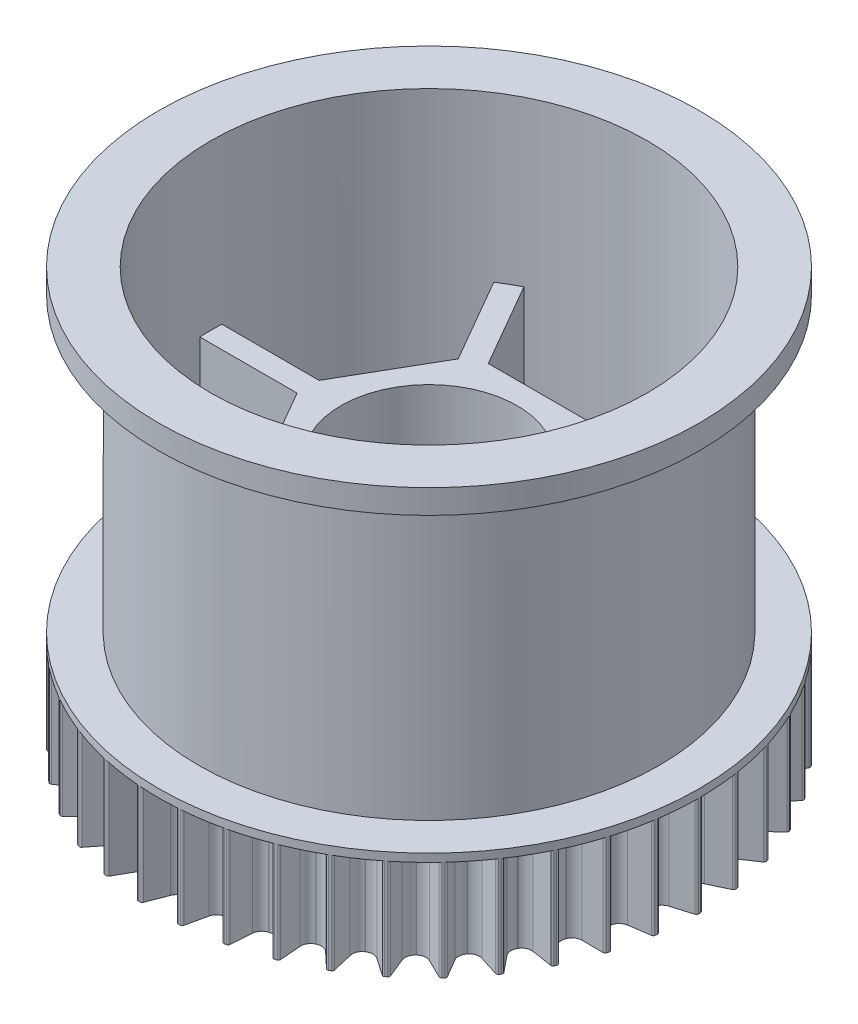
SolidWorks part; units mm, degrees
ref_plane "前视基准面" through (0, 0, 0) normal (0, 0, 1) x (1, 0, 0)
ref_plane "上视基准面" through (0, 0, 0) normal (0, 1, 0) x (1, 0, 0)
ref_plane "右视基准面" through (0, 0, 0) normal (1, 0, 0) x (0, 0, -1)
other "Configuration Table"
sketch "草图1" plane through (0, 0, 0) normal (0, 1, 0) x (1, 0, 0)
  line L0 (0, 0) -> (7.9279, 0) construction
  line L1 (0, 0) -> (0, 4.4256) construction
  line L2 (12.4216, 0.4494) -> (13.4287, 0.1463)
  line L3 (12.4216, -0.4494) -> (13.4287, -0.1463)
  line L4 (12.2159, -2.2957) -> (13.2569, -2.1461)
  line L5 (12.3499, -1.407) -> (13.3005, -1.8568)
  line L6 (11.7373, -4.0908) -> (12.789, -4.098)
  line L7 (12.0023, -3.2319) -> (12.8752, -3.8184)
  line L8 (10.9965, -5.7945) -> (12.0354, -5.9583)
  line L9 (11.3865, -4.9846) -> (12.1623, -5.6947)
  line L10 (10.0101, -7.3687) -> (11.0129, -7.6855)
  line L11 (10.5164, -6.626) -> (11.1777, -7.4438)
  line L12 (8.8, -8.7783) -> (9.7445, -9.2411)
  line L13 (9.4114, -8.1194) -> (9.9434, -9.0266)
  line L14 (7.3934, -9.9918) -> (8.2583, -10.5902)
  line L15 (8.0961, -9.4314) -> (8.487, -10.4078)
  line L16 (5.8216, -10.9822) -> (6.5877, -11.7028)
  line L17 (6.6, -10.5328) -> (6.841, -11.5565)
  line L18 (4.1198, -11.7272) -> (4.7699, -12.5539)
  line L19 (4.9565, -11.3988) -> (5.0422, -12.447)
  line L20 (2.3259, -12.2102) -> (2.8456, -13.1246)
  line L21 (3.2022, -12.0102) -> (3.1308, -13.0595)
  line L22 (0.4801, -12.4205) -> (0.8577, -13.4021)
  line L23 (1.3764, -12.3533) -> (1.1494, -13.3802)
  line L24 (-1.3764, -12.3533) -> (-1.1494, -13.3802)
  line L25 (-0.4801, -12.4205) -> (-0.8577, -13.4021)
  line L26 (-3.2022, -12.0102) -> (-3.1308, -13.0595)
  line L27 (-2.3259, -12.2102) -> (-2.8456, -13.1246)
  line L28 (-4.9565, -11.3988) -> (-5.0422, -12.447)
  line L29 (-4.1198, -11.7272) -> (-4.7699, -12.5539)
  line L30 (-6.6, -10.5328) -> (-6.841, -11.5565)
  line L31 (-5.8216, -10.9822) -> (-6.5877, -11.7028)
  line L32 (-8.0961, -9.4314) -> (-8.487, -10.4078)
  line L33 (-7.3934, -9.9918) -> (-8.2583, -10.5902)
  line L34 (-9.4114, -8.1194) -> (-9.9434, -9.0266)
  line L35 (-8.8, -8.7783) -> (-9.7445, -9.2411)
  line L36 (-10.5164, -6.626) -> (-11.1777, -7.4438)
  line L37 (-10.0101, -7.3687) -> (-11.0129, -7.6855)
  line L38 (-11.3865, -4.9846) -> (-12.1623, -5.6947)
  line L39 (-10.9965, -5.7945) -> (-12.0354, -5.9583)
  line L40 (-12.0023, -3.2319) -> (-12.8752, -3.8184)
  line L41 (-11.7373, -4.0908) -> (-12.789, -4.098)
  line L42 (-12.3499, -1.407) -> (-13.3005, -1.8568)
  line L43 (-12.2159, -2.2957) -> (-13.2569, -2.1461)
  line L44 (-12.4216, 0.4494) -> (-13.4287, 0.1463)
  line L45 (-12.4216, -0.4494) -> (-13.4287, -0.1463)
  line L46 (-12.2159, 2.2957) -> (-13.2569, 2.1461)
  line L47 (-12.3499, 1.407) -> (-13.3005, 1.8568)
  line L48 (-11.7373, 4.0908) -> (-12.789, 4.098)
  line L49 (-12.0023, 3.2319) -> (-12.8752, 3.8184)
  line L50 (-10.9965, 5.7945) -> (-12.0354, 5.9583)
  line L51 (-11.3865, 4.9846) -> (-12.1623, 5.6947)
  line L52 (-10.0101, 7.3687) -> (-11.0129, 7.6855)
  line L53 (-10.5164, 6.626) -> (-11.1777, 7.4438)
  line L54 (-8.8, 8.7783) -> (-9.7445, 9.2411)
  line L55 (-9.4114, 8.1194) -> (-9.9434, 9.0266)
  line L56 (-7.3934, 9.9918) -> (-8.2583, 10.5902)
  line L57 (-8.0961, 9.4314) -> (-8.487, 10.4078)
  line L58 (-5.8216, 10.9822) -> (-6.5877, 11.7028)
  line L59 (-6.6, 10.5328) -> (-6.841, 11.5565)
  line L60 (-4.1198, 11.7272) -> (-4.7699, 12.5539)
  line L61 (-4.9565, 11.3988) -> (-5.0422, 12.447)
  line L62 (-2.3259, 12.2102) -> (-2.8456, 13.1246)
  line L63 (-3.2022, 12.0102) -> (-3.1308, 13.0595)
  line L64 (-0.4801, 12.4205) -> (-0.8577, 13.4021)
  line L65 (-1.3764, 12.3533) -> (-1.1494, 13.3802)
  line L66 (1.3764, 12.3533) -> (1.1494, 13.3802)
  line L67 (0.4801, 12.4205) -> (0.8577, 13.4021)
  line L68 (3.2022, 12.0102) -> (3.1308, 13.0595)
  line L69 (2.3259, 12.2102) -> (2.8456, 13.1246)
  line L70 (4.9565, 11.3988) -> (5.0422, 12.447)
  line L71 (4.1198, 11.7272) -> (4.7699, 12.5539)
  line L72 (6.6, 10.5328) -> (6.841, 11.5565)
  line L73 (5.8216, 10.9822) -> (6.5877, 11.7028)
  line L74 (8.0961, 9.4314) -> (8.487, 10.4078)
  line L75 (7.3934, 9.9918) -> (8.2583, 10.5902)
  line L76 (9.4114, 8.1194) -> (9.9434, 9.0266)
  line L77 (8.8, 8.7783) -> (9.7445, 9.2411)
  line L78 (10.5164, 6.626) -> (11.1777, 7.4438)
  line L79 (10.0101, 7.3687) -> (11.0129, 7.6855)
  line L80 (11.3865, 4.9846) -> (12.1623, 5.6947)
  line L81 (10.9965, 5.7945) -> (12.0354, 5.9583)
  line L82 (12.0023, 3.2319) -> (12.8752, 3.8184)
  line L83 (11.7373, 4.0908) -> (12.789, 4.098)
  line L84 (12.3499, 1.407) -> (13.3005, 1.8568)
  line L85 (12.2159, 2.2957) -> (13.2569, 2.1461)
  line L95 (3.1754, 5.5) -> (-3.1754, 5.5) construction
  line L96 (3.1754, 5.5) -> (6.0333, 0.55) construction
  line L97 (0, 0) -> (3.1754, 5.5) construction
  line L98 (-3.1754, 5.5) -> (-6.0333, 0.55) construction
  line L99 (3.493, -4.95) -> (6.0333, -0.55)
  line L100 (2.5403, -5.5) -> (-2.5403, -5.5)
  line L101 (-3.493, -4.95) -> (-6.0333, -0.55)
  line L102 (8.1752, 0) -> (11.2, 0) construction
  line L103 (6.0333, 0.55) -> (11.1865, 0.55)
  line L104 (6.0333, -0.55) -> (11.1865, -0.55)
  line L105 (3.493, -4.95) -> (6.0696, -9.4128)
  line L106 (2.5403, -5.5) -> (5.1169, -9.9628)
  line L107 (-2.5403, -5.5) -> (-5.1169, -9.9628)
  line L108 (-3.493, -4.95) -> (-6.0696, -9.4128)
  line L109 (-6.0333, -0.55) -> (-11.1865, -0.55)
  line L110 (-6.0333, 0.55) -> (-11.1865, 0.55)
  line L111 (-3.493, 4.95) -> (-6.0696, 9.4128)
  line L112 (-2.5403, 5.5) -> (-5.1169, 9.9628)
  line L113 (2.5403, 5.5) -> (5.1169, 9.9628)
  line L114 (3.493, 4.95) -> (6.0696, 9.4128)
  line L115 (0, 0) -> (12.0337, 1.2648) construction
  line L116 (12.0337, -1.2648) -> (0, 0) construction
  line L117 (-6.0333, 0.55) -> (-3.493, 4.95)
  line L118 (-2.5403, 5.5) -> (2.5403, 5.5)
  line L119 (3.493, 4.95) -> (6.0333, 0.55)
  circle A0 centre (0, 0) radius 11.2 construction
  circle A1 centre (0, 0) radius 12.1 construction
  circle A2 centre (0, 0) radius 13.5 construction
  arc A3 (13.4999, 0.0509) -> (13.4999, -0.0509) centre (0, 0) cw
  arc A4 (12.0671, 0.8914) -> (12.0337, 1.2648) centre (0, 0) ccw construction
  arc A5 (13.4287, -0.1463) -> (13.4999, -0.0509) centre (13.3999, -0.0505) ccw
  arc A6 (13.4287, 0.1463) -> (13.4999, 0.0509) centre (13.3999, 0.0505) cw
  arc A7 (12.0671, -0.8914) -> (12.0337, -1.2648) centre (0, 0) cw construction
  arc A8 (12.4216, -0.4494) -> (12.0671, -0.8914) centre (12.5658, -0.9282) ccw
  arc A9 (12.4216, 0.4494) -> (12.0671, 0.8914) centre (12.5658, 0.9282) cw
  arc A10 (12.2159, -2.2957) -> (11.7995, -2.6799) centre (12.2871, -2.7907) ccw
  arc A11 (12.3499, -1.407) -> (12.0652, -0.9171) centre (12.5638, -0.955) cw
  arc A12 (13.3005, -1.8568) -> (13.3567, -1.9617) centre (13.2578, -1.9472) cw
  arc A13 (13.3567, -1.9617) -> (13.3415, -2.0624) centre (0, 0) cw
  arc A14 (13.2569, -2.1461) -> (13.3415, -2.0624) centre (13.2427, -2.0471) ccw
  arc A15 (11.7373, -4.0908) -> (11.2683, -4.4086) centre (11.7339, -4.5908) ccw
  arc A16 (12.0023, -3.2319) -> (11.7937, -2.7051) centre (12.2811, -2.8169) cw
  arc A17 (12.8752, -3.8184) -> (12.9151, -3.9305) centre (12.8195, -3.9014) cw
  arc A18 (12.9151, -3.9305) -> (12.8851, -4.0278) centre (0, 0) cw
  arc A19 (12.789, -4.098) -> (12.8851, -4.0278) centre (12.7897, -3.998) ccw
  arc A20 (10.9965, -5.7945) -> (10.4854, -6.0388) centre (10.9186, -6.2884) ccw
  arc A21 (11.3865, -4.9846) -> (11.2589, -4.4326) centre (11.7241, -4.6158) cw
  arc A22 (12.1623, -5.6947) -> (12.1851, -5.8115) centre (12.0948, -5.7685) cw
  arc A23 (12.1851, -5.8115) -> (12.1409, -5.9032) centre (0, 0) cw
  arc A24 (12.0354, -5.9583) -> (12.1409, -5.9032) centre (12.051, -5.8595) ccw
  arc A25 (10.0101, -7.3687) -> (9.4682, -7.5341) centre (9.8595, -7.8455) ccw
  arc A26 (10.5164, -6.626) -> (10.4724, -6.0612) centre (10.9052, -6.3116) cw
  arc A27 (11.1777, -7.4438) -> (11.1828, -7.5627) centre (11.1, -7.5067) cw
  arc A28 (11.1828, -7.5627) -> (11.1255, -7.6468) centre (0, 0) cw
  arc A29 (11.0129, -7.6855) -> (11.1255, -7.6468) centre (11.0431, -7.5902) ccw
  arc A30 (8.8, -8.7783) -> (8.2395, -8.8611) centre (8.58, -9.2273) ccw
  arc A31 (9.4114, -8.1194) -> (9.4521, -7.5543) centre (9.8427, -7.8665) cw
  arc A32 (9.9434, -9.0266) -> (9.9308, -9.145) centre (9.8572, -9.0772) cw
  arc A33 (9.9308, -9.145) -> (9.8615, -9.2196) centre (0, 0) cw
  arc A34 (9.7445, -9.2411) -> (9.8615, -9.2196) centre (9.7885, -9.1513) ccw
  arc A35 (7.3934, -9.9918) -> (6.8268, -9.9902) centre (7.1089, -10.403) ccw
  arc A36 (8.0961, -9.4314) -> (8.2206, -8.8787) centre (8.5603, -9.2456) cw
  arc A37 (8.487, -10.4078) -> (8.4568, -10.5229) centre (8.3942, -10.445) cw
  arc A38 (8.4568, -10.5229) -> (8.3773, -10.5864) centre (0, 0) cw
  arc A39 (8.2583, -10.5902) -> (8.3773, -10.5864) centre (8.3152, -10.508) ccw
  arc A40 (5.8216, -10.9822) -> (5.2616, -10.8961) centre (5.479, -11.3464) ccw
  arc A41 (6.6, -10.5328) -> (6.8055, -10.0048) centre (7.0867, -10.4182) cw
  arc A42 (6.841, -11.5565) -> (6.794, -11.6658) centre (6.7437, -11.5794) cw
  arc A43 (6.794, -11.6658) -> (6.7059, -11.7167) centre (0, 0) cw
  arc A44 (6.5877, -11.7028) -> (6.7059, -11.7167) centre (6.6562, -11.6299) ccw
  arc A45 (4.1198, -11.7272) -> (3.5789, -11.5586) centre (3.7268, -12.0362) ccw
  arc A46 (4.9565, -11.3988) -> (5.2384, -10.9073) centre (5.4548, -11.358) cw
  arc A47 (5.0422, -12.447) -> (4.9795, -12.5481) centre (4.9426, -12.4552) cw
  arc A48 (4.9795, -12.5481) -> (4.8847, -12.5853) centre (0, 0) cw
  arc A49 (4.7699, -12.5539) -> (4.8847, -12.5853) centre (4.8485, -12.4921) ccw
  arc A50 (2.3259, -12.2102) -> (1.8162, -11.9629) centre (1.8912, -12.4573) ccw
  arc A51 (3.2022, -12.0102) -> (3.5542, -11.5662) centre (3.7011, -12.0442) cw
  arc A52 (3.1308, -13.0595) -> (3.0536, -13.1501) centre (3.031, -13.0527) cw
  arc A53 (3.0536, -13.1501) -> (2.9544, -13.1728) centre (0, 0) cw
  arc A54 (2.8456, -13.1246) -> (2.9544, -13.1728) centre (2.9325, -13.0752) ccw
  arc A55 (0.4801, -12.4205) -> (0.0129, -12.1) centre (0.0134, -12.6) ccw
  arc A56 (1.3764, -12.3533) -> (1.7906, -11.9668) centre (1.8646, -12.4613) cw
  arc A57 (1.1494, -13.3802) -> (1.0596, -13.4584) centre (1.0518, -13.3587) cw
  arc A58 (1.0596, -13.4584) -> (0.9581, -13.466) centre (0, 0) cw
  arc A59 (0.8577, -13.4021) -> (0.9581, -13.466) centre (0.951, -13.3662) ccw
  arc A60 (-1.3764, -12.3533) -> (-1.7906, -11.9668) centre (-1.8646, -12.4613) ccw
  arc A61 (-0.4801, -12.4205) -> (-0.0129, -12.1) centre (-0.0134, -12.6) cw
  arc A62 (-0.8577, -13.4021) -> (-0.9581, -13.466) centre (-0.951, -13.3662) cw
  arc A63 (-0.9581, -13.466) -> (-1.0596, -13.4584) centre (0, 0) cw
  arc A64 (-1.1494, -13.3802) -> (-1.0596, -13.4584) centre (-1.0518, -13.3587) ccw
  arc A65 (-3.2022, -12.0102) -> (-3.5542, -11.5662) centre (-3.7011, -12.0442) ccw
  arc A66 (-2.3259, -12.2102) -> (-1.8162, -11.9629) centre (-1.8912, -12.4573) cw
  arc A67 (-2.8456, -13.1246) -> (-2.9544, -13.1728) centre (-2.9325, -13.0752) cw
  arc A68 (-2.9544, -13.1728) -> (-3.0536, -13.1501) centre (0, 0) cw
  arc A69 (-3.1308, -13.0595) -> (-3.0536, -13.1501) centre (-3.031, -13.0527) ccw
  arc A70 (-4.9565, -11.3988) -> (-5.2384, -10.9073) centre (-5.4548, -11.358) ccw
  arc A71 (-4.1198, -11.7272) -> (-3.5789, -11.5586) centre (-3.7268, -12.0362) cw
  arc A72 (-4.7699, -12.5539) -> (-4.8847, -12.5853) centre (-4.8485, -12.4921) cw
  arc A73 (-4.8847, -12.5853) -> (-4.9795, -12.5481) centre (0, 0) cw
  arc A74 (-5.0422, -12.447) -> (-4.9795, -12.5481) centre (-4.9426, -12.4552) ccw
  arc A75 (-6.6, -10.5328) -> (-6.8055, -10.0048) centre (-7.0867, -10.4182) ccw
  arc A76 (-5.8216, -10.9822) -> (-5.2616, -10.8961) centre (-5.479, -11.3464) cw
  arc A77 (-6.5877, -11.7028) -> (-6.7059, -11.7167) centre (-6.6562, -11.6299) cw
  arc A78 (-6.7059, -11.7167) -> (-6.794, -11.6658) centre (0, 0) cw
  arc A79 (-6.841, -11.5565) -> (-6.794, -11.6658) centre (-6.7437, -11.5794) ccw
  arc A80 (-8.0961, -9.4314) -> (-8.2206, -8.8787) centre (-8.5603, -9.2456) ccw
  arc A81 (-7.3934, -9.9918) -> (-6.8268, -9.9902) centre (-7.1089, -10.403) cw
  arc A82 (-8.2583, -10.5902) -> (-8.3773, -10.5864) centre (-8.3152, -10.508) cw
  arc A83 (-8.3773, -10.5864) -> (-8.4568, -10.5229) centre (0, 0) cw
  arc A84 (-8.487, -10.4078) -> (-8.4568, -10.5229) centre (-8.3942, -10.445) ccw
  arc A85 (-9.4114, -8.1194) -> (-9.4521, -7.5543) centre (-9.8427, -7.8665) ccw
  arc A86 (-8.8, -8.7783) -> (-8.2395, -8.8611) centre (-8.58, -9.2273) cw
  arc A87 (-9.7445, -9.2411) -> (-9.8615, -9.2196) centre (-9.7885, -9.1513) cw
  arc A88 (-9.8615, -9.2196) -> (-9.9308, -9.145) centre (0, 0) cw
  arc A89 (-9.9434, -9.0266) -> (-9.9308, -9.145) centre (-9.8572, -9.0772) ccw
  arc A90 (-10.5164, -6.626) -> (-10.4724, -6.0612) centre (-10.9052, -6.3116) ccw
  arc A91 (-10.0101, -7.3687) -> (-9.4682, -7.5341) centre (-9.8595, -7.8455) cw
  arc A92 (-11.0129, -7.6855) -> (-11.1255, -7.6468) centre (-11.0431, -7.5902) cw
  arc A93 (-11.1255, -7.6468) -> (-11.1828, -7.5627) centre (0, 0) cw
  arc A94 (-11.1777, -7.4438) -> (-11.1828, -7.5627) centre (-11.1, -7.5067) ccw
  arc A95 (-11.3865, -4.9846) -> (-11.2589, -4.4326) centre (-11.7241, -4.6158) ccw
  arc A96 (-10.9965, -5.7945) -> (-10.4854, -6.0388) centre (-10.9186, -6.2884) cw
  arc A97 (-12.0354, -5.9583) -> (-12.1409, -5.9032) centre (-12.051, -5.8595) cw
  arc A98 (-12.1409, -5.9032) -> (-12.1851, -5.8115) centre (0, 0) cw
  arc A99 (-12.1623, -5.6947) -> (-12.1851, -5.8115) centre (-12.0948, -5.7685) ccw
  arc A100 (-12.0023, -3.2319) -> (-11.7937, -2.7051) centre (-12.2811, -2.8169) ccw
  arc A101 (-11.7373, -4.0908) -> (-11.2683, -4.4086) centre (-11.7339, -4.5908) cw
  arc A102 (-12.789, -4.098) -> (-12.8851, -4.0278) centre (-12.7897, -3.998) cw
  arc A103 (-12.8851, -4.0278) -> (-12.9151, -3.9305) centre (0, 0) cw
  arc A104 (-12.8752, -3.8184) -> (-12.9151, -3.9305) centre (-12.8195, -3.9014) ccw
  arc A105 (-12.3499, -1.407) -> (-12.0652, -0.9171) centre (-12.5638, -0.955) ccw
  arc A106 (-12.2159, -2.2957) -> (-11.7995, -2.6799) centre (-12.2871, -2.7907) cw
  arc A107 (-13.2569, -2.1461) -> (-13.3415, -2.0624) centre (-13.2427, -2.0471) cw
  arc A108 (-13.3415, -2.0624) -> (-13.3567, -1.9617) centre (0, 0) cw
  arc A109 (-13.3005, -1.8568) -> (-13.3567, -1.9617) centre (-13.2578, -1.9472) ccw
  arc A110 (-12.4216, 0.4494) -> (-12.0671, 0.8914) centre (-12.5658, 0.9282) ccw
  arc A111 (-12.4216, -0.4494) -> (-12.0671, -0.8914) centre (-12.5658, -0.9282) cw
  arc A112 (-13.4287, -0.1463) -> (-13.4999, -0.0509) centre (-13.3999, -0.0505) cw
  arc A113 (-13.4999, -0.0509) -> (-13.4999, 0.0509) centre (0, 0) cw
  arc A114 (-13.4287, 0.1463) -> (-13.4999, 0.0509) centre (-13.3999, 0.0505) ccw
  arc A115 (-12.2159, 2.2957) -> (-11.7995, 2.6799) centre (-12.2871, 2.7907) ccw
  arc A116 (-12.3499, 1.407) -> (-12.0652, 0.9171) centre (-12.5638, 0.955) cw
  arc A117 (-13.3005, 1.8568) -> (-13.3567, 1.9617) centre (-13.2578, 1.9472) cw
  arc A118 (-13.3567, 1.9617) -> (-13.3415, 2.0624) centre (0, 0) cw
  arc A119 (-13.2569, 2.1461) -> (-13.3415, 2.0624) centre (-13.2427, 2.0471) ccw
  arc A120 (-11.7373, 4.0908) -> (-11.2683, 4.4086) centre (-11.7339, 4.5908) ccw
  arc A121 (-12.0023, 3.2319) -> (-11.7937, 2.7051) centre (-12.2811, 2.8169) cw
  arc A122 (-12.8752, 3.8184) -> (-12.9151, 3.9305) centre (-12.8195, 3.9014) cw
  arc A123 (-12.9151, 3.9305) -> (-12.8851, 4.0278) centre (0, 0) cw
  arc A124 (-12.789, 4.098) -> (-12.8851, 4.0278) centre (-12.7897, 3.998) ccw
  arc A125 (-10.9965, 5.7945) -> (-10.4854, 6.0388) centre (-10.9186, 6.2884) ccw
  arc A126 (-11.3865, 4.9846) -> (-11.2589, 4.4326) centre (-11.7241, 4.6158) cw
  arc A127 (-12.1623, 5.6947) -> (-12.1851, 5.8115) centre (-12.0948, 5.7685) cw
  arc A128 (-12.1851, 5.8115) -> (-12.1409, 5.9032) centre (0, 0) cw
  arc A129 (-12.0354, 5.9583) -> (-12.1409, 5.9032) centre (-12.051, 5.8595) ccw
  arc A130 (-10.0101, 7.3687) -> (-9.4682, 7.5341) centre (-9.8595, 7.8455) ccw
  arc A131 (-10.5164, 6.626) -> (-10.4724, 6.0612) centre (-10.9052, 6.3116) cw
  arc A132 (-11.1777, 7.4438) -> (-11.1828, 7.5627) centre (-11.1, 7.5067) cw
  arc A133 (-11.1828, 7.5627) -> (-11.1255, 7.6468) centre (0, 0) cw
  arc A134 (-11.0129, 7.6855) -> (-11.1255, 7.6468) centre (-11.0431, 7.5902) ccw
  arc A135 (-8.8, 8.7783) -> (-8.2395, 8.8611) centre (-8.58, 9.2273) ccw
  arc A136 (-9.4114, 8.1194) -> (-9.4521, 7.5543) centre (-9.8427, 7.8665) cw
  arc A137 (-9.9434, 9.0266) -> (-9.9308, 9.145) centre (-9.8572, 9.0772) cw
  arc A138 (-9.9308, 9.145) -> (-9.8615, 9.2196) centre (0, 0) cw
  arc A139 (-9.7445, 9.2411) -> (-9.8615, 9.2196) centre (-9.7885, 9.1513) ccw
  arc A140 (-7.3934, 9.9918) -> (-6.8268, 9.9902) centre (-7.1089, 10.403) ccw
  arc A141 (-8.0961, 9.4314) -> (-8.2206, 8.8787) centre (-8.5603, 9.2456) cw
  arc A142 (-8.487, 10.4078) -> (-8.4568, 10.5229) centre (-8.3942, 10.445) cw
  arc A143 (-8.4568, 10.5229) -> (-8.3773, 10.5864) centre (0, 0) cw
  arc A144 (-8.2583, 10.5902) -> (-8.3773, 10.5864) centre (-8.3152, 10.508) ccw
  arc A145 (-5.8216, 10.9822) -> (-5.2616, 10.8961) centre (-5.479, 11.3464) ccw
  arc A146 (-6.6, 10.5328) -> (-6.8055, 10.0048) centre (-7.0867, 10.4182) cw
  arc A147 (-6.841, 11.5565) -> (-6.794, 11.6658) centre (-6.7437, 11.5794) cw
  arc A148 (-6.794, 11.6658) -> (-6.7059, 11.7167) centre (0, 0) cw
  arc A149 (-6.5877, 11.7028) -> (-6.7059, 11.7167) centre (-6.6562, 11.6299) ccw
  arc A150 (-4.1198, 11.7272) -> (-3.5789, 11.5586) centre (-3.7268, 12.0362) ccw
  arc A151 (-4.9565, 11.3988) -> (-5.2384, 10.9073) centre (-5.4548, 11.358) cw
  arc A152 (-5.0422, 12.447) -> (-4.9795, 12.5481) centre (-4.9426, 12.4552) cw
  arc A153 (-4.9795, 12.5481) -> (-4.8847, 12.5853) centre (0, 0) cw
  arc A154 (-4.7699, 12.5539) -> (-4.8847, 12.5853) centre (-4.8485, 12.4921) ccw
  arc A155 (-2.3259, 12.2102) -> (-1.8162, 11.9629) centre (-1.8912, 12.4573) ccw
  arc A156 (-3.2022, 12.0102) -> (-3.5542, 11.5662) centre (-3.7011, 12.0442) cw
  arc A157 (-3.1308, 13.0595) -> (-3.0536, 13.1501) centre (-3.031, 13.0527) cw
  arc A158 (-3.0536, 13.1501) -> (-2.9544, 13.1728) centre (0, 0) cw
  arc A159 (-2.8456, 13.1246) -> (-2.9544, 13.1728) centre (-2.9325, 13.0752) ccw
  arc A160 (-0.4801, 12.4205) -> (-0.0129, 12.1) centre (-0.0134, 12.6) ccw
  arc A161 (-1.3764, 12.3533) -> (-1.7906, 11.9668) centre (-1.8646, 12.4613) cw
  arc A162 (-1.1494, 13.3802) -> (-1.0596, 13.4584) centre (-1.0518, 13.3587) cw
  arc A163 (-1.0596, 13.4584) -> (-0.9581, 13.466) centre (0, 0) cw
  arc A164 (-0.8577, 13.4021) -> (-0.9581, 13.466) centre (-0.951, 13.3662) ccw
  arc A165 (1.3764, 12.3533) -> (1.7906, 11.9668) centre (1.8646, 12.4613) ccw
  arc A166 (0.4801, 12.4205) -> (0.0129, 12.1) centre (0.0134, 12.6) cw
  arc A167 (0.8577, 13.4021) -> (0.9581, 13.466) centre (0.951, 13.3662) cw
  arc A168 (0.9581, 13.466) -> (1.0596, 13.4584) centre (0, 0) cw
  arc A169 (1.1494, 13.3802) -> (1.0596, 13.4584) centre (1.0518, 13.3587) ccw
  arc A170 (3.2022, 12.0102) -> (3.5542, 11.5662) centre (3.7011, 12.0442) ccw
  arc A171 (2.3259, 12.2102) -> (1.8162, 11.9629) centre (1.8912, 12.4573) cw
  arc A172 (2.8456, 13.1246) -> (2.9544, 13.1728) centre (2.9325, 13.0752) cw
  arc A173 (2.9544, 13.1728) -> (3.0536, 13.1501) centre (0, 0) cw
  arc A174 (3.1308, 13.0595) -> (3.0536, 13.1501) centre (3.031, 13.0527) ccw
  arc A175 (4.9565, 11.3988) -> (5.2384, 10.9073) centre (5.4548, 11.358) ccw
  arc A176 (4.1198, 11.7272) -> (3.5789, 11.5586) centre (3.7268, 12.0362) cw
  arc A177 (4.7699, 12.5539) -> (4.8847, 12.5853) centre (4.8485, 12.4921) cw
  arc A178 (4.8847, 12.5853) -> (4.9795, 12.5481) centre (0, 0) cw
  arc A179 (5.0422, 12.447) -> (4.9795, 12.5481) centre (4.9426, 12.4552) ccw
  arc A180 (6.6, 10.5328) -> (6.8055, 10.0048) centre (7.0867, 10.4182) ccw
  arc A181 (5.8216, 10.9822) -> (5.2616, 10.8961) centre (5.479, 11.3464) cw
  arc A182 (6.5877, 11.7028) -> (6.7059, 11.7167) centre (6.6562, 11.6299) cw
  arc A183 (6.7059, 11.7167) -> (6.794, 11.6658) centre (0, 0) cw
  arc A184 (6.841, 11.5565) -> (6.794, 11.6658) centre (6.7437, 11.5794) ccw
  arc A185 (8.0961, 9.4314) -> (8.2206, 8.8787) centre (8.5603, 9.2456) ccw
  arc A186 (7.3934, 9.9918) -> (6.8268, 9.9902) centre (7.1089, 10.403) cw
  arc A187 (8.2583, 10.5902) -> (8.3773, 10.5864) centre (8.3152, 10.508) cw
  arc A188 (8.3773, 10.5864) -> (8.4568, 10.5229) centre (0, 0) cw
  arc A189 (8.487, 10.4078) -> (8.4568, 10.5229) centre (8.3942, 10.445) ccw
  arc A190 (9.4114, 8.1194) -> (9.4521, 7.5543) centre (9.8427, 7.8665) ccw
  arc A191 (8.8, 8.7783) -> (8.2395, 8.8611) centre (8.58, 9.2273) cw
  arc A192 (9.7445, 9.2411) -> (9.8615, 9.2196) centre (9.7885, 9.1513) cw
  arc A193 (9.8615, 9.2196) -> (9.9308, 9.145) centre (0, 0) cw
  arc A194 (9.9434, 9.0266) -> (9.9308, 9.145) centre (9.8572, 9.0772) ccw
  arc A195 (10.5164, 6.626) -> (10.4724, 6.0612) centre (10.9052, 6.3116) ccw
  arc A196 (10.0101, 7.3687) -> (9.4682, 7.5341) centre (9.8595, 7.8455) cw
  arc A197 (11.0129, 7.6855) -> (11.1255, 7.6468) centre (11.0431, 7.5902) cw
  arc A198 (11.1255, 7.6468) -> (11.1828, 7.5627) centre (0, 0) cw
  arc A199 (11.1777, 7.4438) -> (11.1828, 7.5627) centre (11.1, 7.5067) ccw
  arc A200 (11.3865, 4.9846) -> (11.2589, 4.4326) centre (11.7241, 4.6158) ccw
  arc A201 (10.9965, 5.7945) -> (10.4854, 6.0388) centre (10.9186, 6.2884) cw
  arc A202 (12.0354, 5.9583) -> (12.1409, 5.9032) centre (12.051, 5.8595) cw
  arc A203 (12.1409, 5.9032) -> (12.1851, 5.8115) centre (0, 0) cw
  arc A204 (12.1623, 5.6947) -> (12.1851, 5.8115) centre (12.0948, 5.7685) ccw
  arc A205 (12.0023, 3.2319) -> (11.7937, 2.7051) centre (12.2811, 2.8169) ccw
  arc A206 (11.7373, 4.0908) -> (11.2683, 4.4086) centre (11.7339, 4.5908) cw
  arc A207 (12.789, 4.098) -> (12.8851, 4.0278) centre (12.7897, 3.998) cw
  arc A208 (12.8851, 4.0278) -> (12.9151, 3.9305) centre (0, 0) cw
  arc A209 (12.8752, 3.8184) -> (12.9151, 3.9305) centre (12.8195, 3.9014) ccw
  arc A210 (12.3499, 1.407) -> (12.0652, 0.9171) centre (12.5638, 0.955) ccw
  arc A211 (12.2159, 2.2957) -> (11.7995, 2.6799) centre (12.2871, 2.7907) cw
  arc A212 (13.2569, 2.1461) -> (13.3415, 2.0624) centre (13.2427, 2.0471) cw
  arc A213 (13.3415, 2.0624) -> (13.3567, 1.9617) centre (0, 0) cw
  arc A214 (13.3005, 1.8568) -> (13.3567, 1.9617) centre (13.2578, 1.9472) ccw
  circle A216 centre (0, 0) radius 4.4
  arc A217 (11.1865, 0.55) -> (6.0696, 9.4128) centre (0, 0) ccw
  arc A218 (5.1169, 9.9628) -> (-5.1169, 9.9628) centre (0, 0) ccw
  arc A219 (-6.0696, 9.4128) -> (-11.1865, 0.55) centre (0, 0) ccw
  arc A220 (-11.1865, -0.55) -> (-6.0696, -9.4128) centre (0, 0) ccw
  arc A221 (-5.1169, -9.9628) -> (5.1169, -9.9628) centre (0, 0) ccw
  arc A222 (6.0696, -9.4128) -> (11.1865, -0.55) centre (0, 0) ccw
  arc A223 (12.0652, 0.9171) -> (12.0671, 0.8914) centre (0, 0) cw
  arc A224 (12.0671, -0.8914) -> (12.0652, -0.9171) centre (0, 0) cw
  arc A225 (11.7995, -2.6799) -> (11.7937, -2.7051) centre (0, 0) cw
  arc A226 (11.2683, -4.4086) -> (11.2589, -4.4326) centre (0, 0) cw
  arc A227 (10.4854, -6.0388) -> (10.4724, -6.0612) centre (0, 0) cw
  arc A228 (9.4682, -7.5341) -> (9.4521, -7.5543) centre (0, 0) cw
  arc A229 (8.2395, -8.8611) -> (8.2206, -8.8787) centre (0, 0) cw
  arc A230 (6.8268, -9.9902) -> (6.8055, -10.0048) centre (0, 0) cw
  arc A231 (5.2616, -10.8961) -> (5.2384, -10.9073) centre (0, 0) cw
  arc A232 (3.5789, -11.5586) -> (3.5542, -11.5662) centre (0, 0) cw
  arc A233 (1.8162, -11.9629) -> (1.7906, -11.9668) centre (0, 0) cw
  arc A234 (0.0129, -12.1) -> (-0.0129, -12.1) centre (0, 0) cw
  arc A235 (-1.7906, -11.9668) -> (-1.8162, -11.9629) centre (0, 0) cw
  arc A236 (-3.5542, -11.5662) -> (-3.5789, -11.5586) centre (0, 0) cw
  arc A237 (-5.2384, -10.9073) -> (-5.2616, -10.8961) centre (0, 0) cw
  arc A238 (-6.8055, -10.0048) -> (-6.8268, -9.9902) centre (0, 0) cw
  arc A239 (-8.2206, -8.8787) -> (-8.2395, -8.8611) centre (0, 0) cw
  arc A240 (-9.4521, -7.5543) -> (-9.4682, -7.5341) centre (0, 0) cw
  arc A241 (-10.4724, -6.0612) -> (-10.4854, -6.0388) centre (0, 0) cw
  arc A242 (-11.2589, -4.4326) -> (-11.2683, -4.4086) centre (0, 0) cw
  arc A243 (-11.7937, -2.7051) -> (-11.7995, -2.6799) centre (0, 0) cw
  arc A244 (-12.0652, -0.9171) -> (-12.0671, -0.8914) centre (0, 0) cw
  arc A245 (-12.0671, 0.8914) -> (-12.0652, 0.9171) centre (0, 0) cw
  arc A246 (-11.7995, 2.6799) -> (-11.7937, 2.7051) centre (0, 0) cw
  arc A247 (-11.2683, 4.4086) -> (-11.2589, 4.4326) centre (0, 0) cw
  arc A248 (-10.4854, 6.0388) -> (-10.4724, 6.0612) centre (0, 0) cw
  arc A249 (-9.4682, 7.5341) -> (-9.4521, 7.5543) centre (0, 0) cw
  arc A250 (-8.2395, 8.8611) -> (-8.2206, 8.8787) centre (0, 0) cw
  arc A251 (-6.8268, 9.9902) -> (-6.8055, 10.0048) centre (0, 0) cw
  arc A252 (-5.2616, 10.8961) -> (-5.2384, 10.9073) centre (0, 0) cw
  arc A253 (-3.5789, 11.5586) -> (-3.5542, 11.5662) centre (0, 0) cw
  arc A254 (-1.8162, 11.9629) -> (-1.7906, 11.9668) centre (0, 0) cw
  arc A255 (-0.0129, 12.1) -> (0.0129, 12.1) centre (0, 0) cw
  arc A256 (1.7906, 11.9668) -> (1.8162, 11.9629) centre (0, 0) cw
  arc A257 (3.5542, 11.5662) -> (3.5789, 11.5586) centre (0, 0) cw
  arc A258 (5.2384, 10.9073) -> (5.2616, 10.8961) centre (0, 0) cw
  arc A259 (6.8055, 10.0048) -> (6.8268, 9.9902) centre (0, 0) cw
  arc A260 (8.2206, 8.8787) -> (8.2395, 8.8611) centre (0, 0) cw
  arc A261 (9.4521, 7.5543) -> (9.4682, 7.5341) centre (0, 0) cw
  arc A262 (10.4724, 6.0612) -> (10.4854, 6.0388) centre (0, 0) cw
  arc A263 (11.2589, 4.4326) -> (11.2683, 4.4086) centre (0, 0) cw
  arc A264 (11.7937, 2.7051) -> (11.7995, 2.6799) centre (0, 0) cw
  circle A265 centre (0, 0) radius 3.5
  point P17 (13.4994, -0.125)
  point P20 (13.4994, 0.125)
  point P23 (12.0875, -0.55)
  point P26 (12.0875, 0.55)
  point P524 (0, 5.5)
  dimension "D1" = 22.4
  dimension "D2" = 24.2
  dimension "D3" = 27
  dimension "D6" = 0.1
  dimension "D7" = 0.5
  dimension "D9" = 120
  dimension "D12" = 8.8
  dimension "D14" = 7
  dimension "D4" = 1.1
  dimension "D5" = 0.25
  dimension "D10" = 5.5
  dimension "D11" = 30
  dimension "D16" = 6
  dimension "D17" = 6
  dimension "D8" = 42
  dimension "D13" = 6
  dimension "D15" = 42
extrude "凸台-拉伸1" add sketch "草图1" along normal blind 5 contours A264 A205 L82 A209 A208 A207 L83 A206 A263 A200 L80 A204 A203 A202 L81 A201 A262 A195 L78 A199 A198 A197 L79 A196 A261 A190 L76 A194 A193 A192 L77 A191 A260 A185 L74 A189 A188 A187 L75 A186 A259 A180 L72 A184 A183 A182 L73 A181 A258 A175 L70 region at (12.8153, 0, 0.0673)
sketch "草图2" plane through (0, 5, 0) normal (0, 1, 0) x (1, 0, 0)
  circle A0 centre (0, 0) radius 13.5
  circle A2 centre (0, 0) radius 11.2
  arc A4 (11.1865, 0.55) -> (6.0696, 9.4128) centre (0, 0) ccw construction
  dimension "D1" = 27
extrude "凸台-拉伸2" add sketch "草图2" along normal blind 0.4 contours A0 A2 | A2 | A0 region at (-13.1182, 5, 0)
extrude "拉伸-薄壁2" add sketch "草图2<2>" along normal blind 15 thin contours A2 thin type mid plane wall 0.6
sketch "草图2<2>" plane through (0, 5, 0) normal (0, 1, 0) x (1, 0, 0) same geometry as "草图2"
sketch "草图5" plane through (0, 20, 0) normal (0, 1, 0) x (1, 0, 0)
  circle A0 centre (0, 0) radius 13.5
  circle A2 centre (0, 0) radius 10.9
  circle A3 centre (0, 0) radius 10.9 construction
  dimension "D1" = 27
extrude "凸台-拉伸3" add sketch "草图5" along normal blind 1.2
sketch "草图6" plane through (0, 5, 0) normal (0, 1, 0) x (1, 0, 0)
  line L18 (-4.9667, -9.7027) -> (-2.5403, -5.5)
  line L19 (-2.5403, -5.5) -> (2.5403, -5.5)
  line L20 (2.5403, -5.5) -> (4.9667, -9.7027)
  line L21 (5.9194, -9.1527) -> (3.493, -4.95)
  line L22 (3.493, -4.95) -> (6.0333, -0.55)
  line L23 (6.0333, -0.55) -> (10.8861, -0.55)
  line L24 (10.8861, 0.55) -> (6.0333, 0.55)
  line L25 (6.0333, 0.55) -> (3.493, 4.95)
  line L26 (3.493, 4.95) -> (5.9194, 9.1527)
  line L27 (4.9667, 9.7027) -> (2.5403, 5.5)
  line L28 (2.5403, 5.5) -> (-2.5403, 5.5)
  line L29 (-2.5403, 5.5) -> (-4.9667, 9.7027)
  line L30 (-5.9194, 9.1527) -> (-3.493, 4.95)
  line L31 (-3.493, 4.95) -> (-6.0333, 0.55)
  line L32 (-6.0333, 0.55) -> (-10.8861, 0.55)
  line L33 (-10.8861, -0.55) -> (-6.0333, -0.55)
  line L34 (-6.0333, -0.55) -> (-3.493, -4.95)
  line L35 (-3.493, -4.95) -> (-5.9194, -9.1527)
  line L36 (-4.9667, -9.7027) -> (-2.5403, -5.5)
  line L37 (-2.5403, -5.5) -> (2.5403, -5.5)
  line L38 (2.5403, -5.5) -> (4.9667, -9.7027)
  line L39 (5.9194, -9.1527) -> (3.493, -4.95)
  line L40 (3.493, -4.95) -> (6.0333, -0.55)
  line L41 (6.0333, -0.55) -> (10.8861, -0.55)
  line L42 (10.8861, 0.55) -> (6.0333, 0.55)
  line L43 (6.0333, 0.55) -> (3.493, 4.95)
  line L44 (3.493, 4.95) -> (5.9194, 9.1527)
  line L45 (4.9667, 9.7027) -> (2.5403, 5.5)
  line L46 (2.5403, 5.5) -> (-2.5403, 5.5)
  line L47 (-2.5403, 5.5) -> (-4.9667, 9.7027)
  line L48 (-5.9194, 9.1527) -> (-3.493, 4.95)
  line L49 (-3.493, 4.95) -> (-6.0333, 0.55)
  line L50 (-6.0333, 0.55) -> (-10.8861, 0.55)
  line L51 (-10.8861, -0.55) -> (-6.0333, -0.55)
  line L52 (-6.0333, -0.55) -> (-3.493, -4.95)
  line L53 (-3.493, -4.95) -> (-5.9194, -9.1527)
  circle A0 centre (0, 0) radius 4.4
  circle A1 centre (0, 0) radius 4.4 construction
  arc A6 (-5.9194, -9.1527) -> (-4.9667, -9.7027) centre (0, 0) ccw
  arc A7 (4.9667, -9.7027) -> (5.9194, -9.1527) centre (0, 0) ccw
  arc A8 (10.8861, -0.55) -> (10.8861, 0.55) centre (0, 0) ccw
  arc A9 (5.9194, 9.1527) -> (4.9667, 9.7027) centre (0, 0) ccw
  arc A10 (-4.9667, 9.7027) -> (-5.9194, 9.1527) centre (0, 0) ccw
  arc A11 (-10.8861, 0.55) -> (-10.8861, -0.55) centre (0, 0) ccw
  arc A12 (-5.9194, -9.1527) -> (-4.9667, -9.7027) centre (0, 0) ccw
  arc A13 (4.9667, -9.7027) -> (5.9194, -9.1527) centre (0, 0) ccw
  arc A14 (10.8861, -0.55) -> (10.8861, 0.55) centre (0, 0) ccw
  arc A15 (5.9194, 9.1527) -> (4.9667, 9.7027) centre (0, 0) ccw
  arc A16 (-4.9667, 9.7027) -> (-5.9194, 9.1527) centre (0, 0) ccw
  arc A17 (-10.8861, 0.55) -> (-10.8861, -0.55) centre (0, 0) ccw
  dimension "D1" = 0
extrude "凸台-拉伸4" add sketch "草图6" along normal blind 8
extrude "凸台-拉伸5" add sketch "草图1<6>" along normal up to surface (13 mm away) contours A216 A265 region at (-4.2755, 0, 0) up to face at (0, 13, 0)
sketch "草图1<6>" plane through (0, 0, 0) normal (0, 1, 0) x (1, 0, 0) same geometry as "草图1"
extrude "切除-拉伸1" cut sketch "草图1<7>" along normal blind 3 contours A216 A265 region at (-4.2755, 0, 0)
sketch "草图1<7>" plane through (0, 0, 0) normal (0, 1, 0) x (1, 0, 0) same geometry as "草图1"
sketch "草图8" plane through (0, 13, 0) normal (0, 1, 0) x (1, 0, 0)
  circle A0 centre (0, 0) radius 4.4
  circle A1 centre (0, 0) radius 3.5
  circle A4 centre (0, 0) radius 3.5 construction
  dimension "D1" = 8.8
extrude "切除-拉伸2" cut sketch "草图8" against normal blind 3
